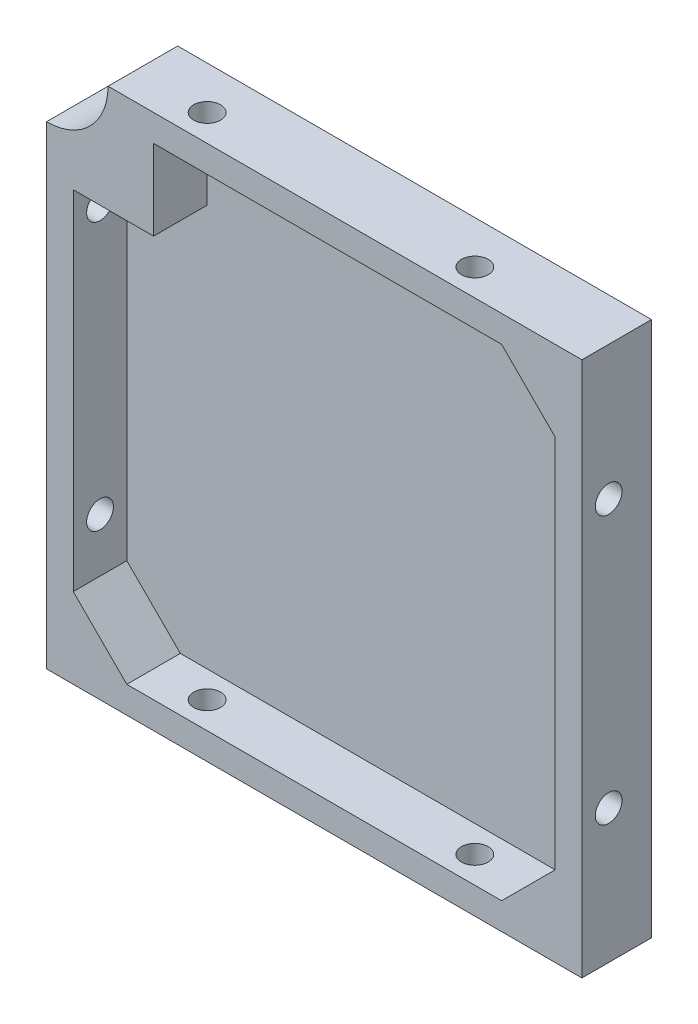
SolidWorks part; units mm, degrees
ref_plane "Plan de face" through (0, 0, 0) normal (0, 0, 1) x (1, 0, 0)
ref_plane "Plan de dessus" through (0, 0, 0) normal (0, 1, 0) x (1, 0, 0)
ref_plane "Plan de droite" through (0, 0, 0) normal (1, 0, 0) x (0, 0, -1)
sketch "Esquisse1" plane through (0, 0, 0) normal (0, 0, 1) x (1, 0, 0)
  line L0 (44.1184, 33.7284) -> (54.1184, 33.7284)
  line L1 (-45.8816, 33.7284) -> (44.1184, 33.7284)
  line L2 (-45.8816, 33.7284) -> (-45.8816, -66.2716)
  line L3 (-45.8816, -66.2716) -> (54.1184, -66.2716)
  line L4 (54.1184, 23.7284) -> (54.1184, -66.2716)
  line L5 (54.1184, 33.7284) -> (54.1184, 23.7284)
  point P6 (54.1184, 33.7284)
  dimension "D1" = 100
  dimension "D2" = 100
extrude "Boss.-Extru.1" add sketch "Esquisse1" along normal blind 13
shell "Coque1" thickness 5 removed face at (4.1184, -16.2716, 13)
sketch "Esquisse2" plane through (-45.8816, 0, 0) normal (-1, 0, 0) x (0, 0, 1)
  line L0 (13, 33.7284) -> (13, -66.2716) construction
  line L1 (13, 33.7284) -> (0, 33.7284) construction
  line L2 (13, -66.2716) -> (0, -66.2716) construction
  circle A0 centre (8, 8.7284) radius 2.5
  circle A1 centre (8, -41.2716) radius 2.5
  dimension "D1" = 5
  dimension "D2" = 5
  dimension "D3" = 5
  dimension "D4" = 5
  dimension "D5" = 25
  dimension "D6" = 25
extrude "Enlèv. mat.-Extru.1" cut sketch "Esquisse2" against normal up to surface (100 mm away) contours A1 | A0 region at (-45.8816, -41.2716, 8) up to face at (54.1184, -16.2716, 6.5)
sketch "Esquisse3" plane through (0, -66.2716, 0) normal (0, -1, 0) x (1, 0, 0)
  line L0 (-45.8816, 13) -> (54.1184, 13) construction
  line L2 (54.1184, 13) -> (54.1184, 0) construction
  line L3 (-45.8816, 13) -> (-45.8816, 0) construction
  circle A0 centre (-20.8816, 8) radius 2.5
  circle A1 centre (29.1184, 8) radius 2.5
  dimension "D1" = 5
  dimension "D2" = 5
  dimension "D3" = 5
  dimension "D4" = 5
  dimension "D5" = 25
  dimension "D6" = 25
extrude "Enlèv. mat.-Extru.2" cut sketch "Esquisse3" against normal up to surface (100 mm away) up to face at (4.1184, 33.7284, 6.5)
sketch "Esquisse4" plane through (0, 0, 3) normal (0, 0, 1) x (1, 0, 0)
  line L0 (-40.8816, -51.2716) -> (-30.8816, -61.2716)
  line L1 (49.1184, 28.7284) -> (-40.8816, 28.7284) construction
  line L3 (-40.8816, 28.7284) -> (-40.8816, -61.2716) construction
  line L4 (-30.8816, -61.2716) -> (-40.8816, -61.2716)
  line L5 (49.1184, 28.7284) -> (49.1184, 18.7284)
  line L6 (49.1184, -61.2716) -> (49.1184, 28.7284) construction
  line L7 (49.1184, 18.7284) -> (39.1184, 28.7284)
  line L8 (39.1184, 28.7284) -> (49.1184, 28.7284)
  line L9 (49.1184, 28.7284) -> (-40.8816, 28.7284) construction
  line L10 (49.1184, -61.2716) -> (49.1184, -51.2716)
  line L11 (49.1184, -51.2716) -> (39.1184, -61.2716)
  line L12 (-40.8816, -61.2716) -> (49.1184, -61.2716) construction
  line L13 (39.1184, -61.2716) -> (49.1184, -61.2716)
  line L14 (-40.8816, -61.2716) -> (-40.8816, -51.2716)
  line L16 (-40.8816, 28.7284) -> (-25.8816, 28.7284)
  line L17 (-40.8816, 28.7284) -> (-40.8816, 13.7284)
  line L18 (-40.8816, 13.7284) -> (-25.8816, 13.7284)
  line L19 (-25.8816, 28.7284) -> (-25.8816, 13.7284)
  dimension "D1" = 10
  dimension "D2" = 10
  dimension "D3" = 10
  dimension "D4" = 10
  dimension "D5" = 10
  dimension "D6" = 10
  dimension "D7" = 15
  dimension "D8" = 15
extrude "Boss.-Extru.2" add sketch "Esquisse4" along normal up to surface (10 mm away) up to face at (4.1184, -16.2716, 13)
sketch "Esquisse5" plane through (0, 0, 13) normal (0, 0, 1) x (1, 0, 0)
  line L0 (54.1184, 33.7284) -> (-45.8816, 33.7284) construction
  line L1 (-45.8816, 33.7284) -> (-45.8816, -66.2716) construction
  circle A0 centre (-45.8816, 33.7284) radius 11.5
  dimension "D1" = 23
extrude "Enlèv. mat.-Extru.3" cut sketch "Esquisse5" against normal up to surface (13 mm away) up to face at (4.1184, -16.2716, 0)
